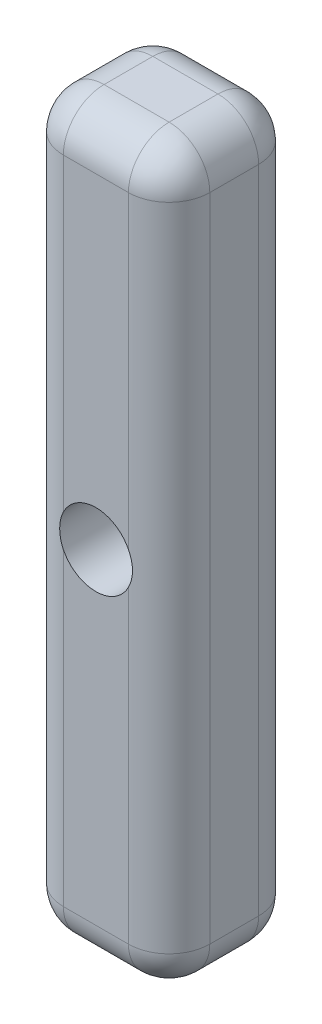
SolidWorks part; units mm, degrees
ref_plane "Front Plane" through (0, 0, 0) normal (1, 0, 0) x (0, 1, 0)
ref_plane "Top Plane" through (0, 0, 0) normal (0, 0, 1) x (0, 1, 0)
ref_plane "Right Plane" through (0, 0, 0) normal (0, 1, 0) x (-1, 0, 0)
sketch "Sketch7" plane through (0, 0, 0) normal (0, 0, 1) x (0, 1, 0)
  line L1 (-45, -9) -> (45, -9)
  line L2 (-45, -9) -> (-45, 9)
  line L3 (-45, 9) -> (45, 9)
  line L4 (45, -9) -> (45, 9)
  line L5 (-45, -9) -> (45, 9) construction
  line L6 (-45, 9) -> (45, -9) construction
  point P0 (0, 0)
  dimension "D1" = 18
  dimension "D2" = 90
extrude "Boss-Extrude1" add sketch "Sketch7" along normal blind 16
sketch "Sketch8" plane through (0, 0, 16) normal (0, 0, 1) x (0, -1, 0)
  circle A0 centre (0, 0) radius 4.475
  dimension "D1" = 8.95
extrude "Cut-Extrude2" cut sketch "Sketch8" against normal blind 12.7
fillet "Fillet1" radius 5 12 edges at (-9, 0, 16) (9, 0, 16) (9, 45, 8) (0, 45, 16) (-9, 45, 8) (-9, 0, 0) (9, 0, 0) (0, 45, 0) (-9, -45, 8) (0, -45, 16) (9, -45, 8) (0, -45, 0)
